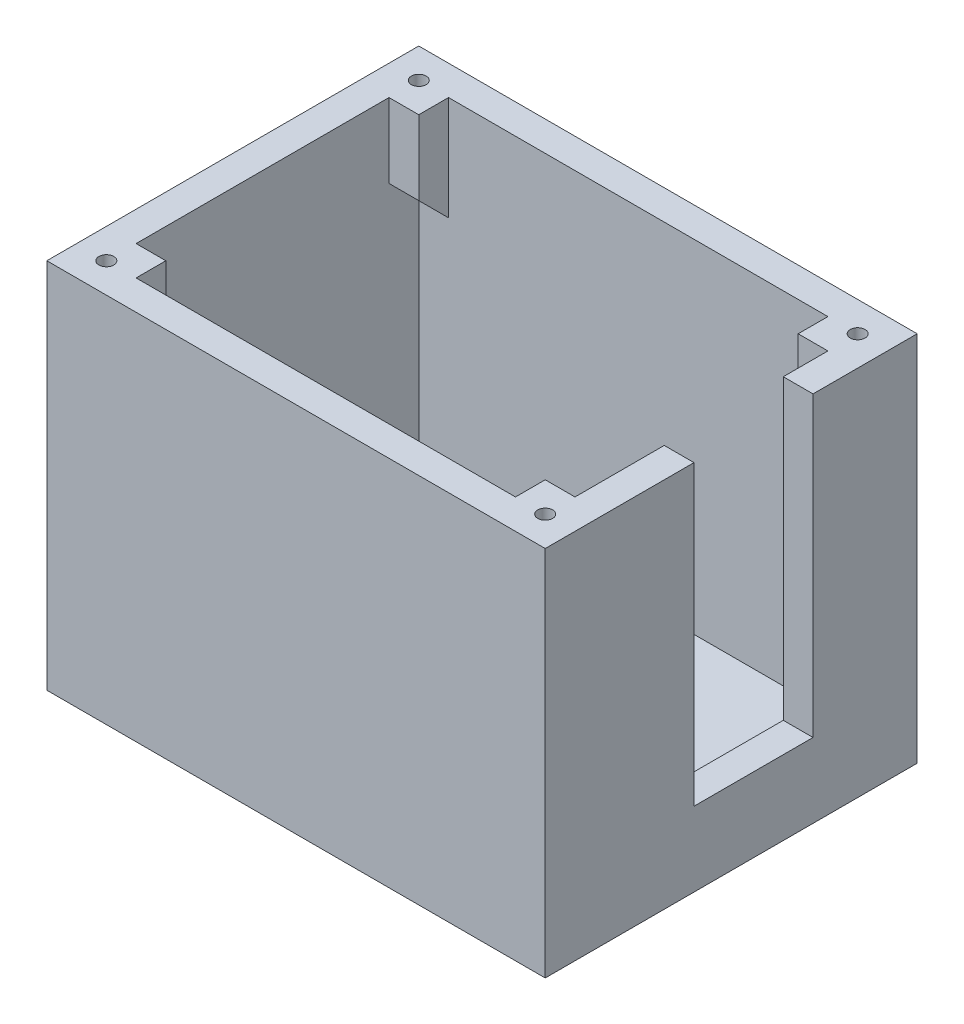
SolidWorks part; units mm, degrees
ref_plane "Front Plane" through (0, 0, 0) normal (0, 0, 1) x (1, 0, 0)
ref_plane "Top Plane" through (0, 0, 0) normal (0, 1, 0) x (1, 0, 0)
ref_plane "Right Plane" through (0, 0, 0) normal (1, 0, 0) x (0, 0, -1)
sketch "Sketch1" plane through (0, 0, 0) normal (0, 1, 0) x (1, 0, 0)
  line L0 (-11.5455, 18.4394) -> (21.9545, 18.4394)
  line L1 (-9.5455, -4.5606) -> (19.9545, -4.5606)
  line L2 (-9.5455, -4.5606) -> (-9.5455, 16.4394)
  line L3 (-9.5455, 16.4394) -> (19.9545, 16.4394)
  line L4 (19.9545, -4.5606) -> (19.9545, 16.4394)
  line L5 (21.9545, -6.5606) -> (21.9545, 18.4394)
  line L6 (-11.5455, -6.5606) -> (21.9545, -6.5606)
  line L7 (-11.5455, -6.5606) -> (-11.5455, 18.4394)
  dimension "D1" = 21
  dimension "D2" = 29.5
  dimension "D3" = 2
extrude "Boss-Extrude1" add sketch "Sketch1" along normal blind 2 contours L1 L4 L3 L2 | L7 L6 L5 L0 L4 L1 L2 L3 region at (5.2045, 0, -18.0214) region at (5.2045, 0, -5.9394)
extrude "Boss-Extrude2" add sketch "Sketch1<3>" along normal offset from surface (25 mm away) 23 up to face at (5.2045, 2, -5.9394) offset beyond the face yes
sketch "Sketch1<3>" plane through (0, 0, 0) normal (0, 1, 0) x (1, 0, 0) same geometry as "Sketch1"
sketch "Sketch2" plane through (0, 25, 0) normal (0, 1, 0) x (1, 0, 0)
  line L0 (19.9545, -4.5606) -> (19.9545, 16.4394) construction
  line L1 (19.9545, 3.4394) -> (21.9545, 3.4394)
  line L2 (19.9545, 3.4394) -> (19.9545, 11.4394)
  line L3 (19.9545, 11.4394) -> (21.9545, 11.4394)
  line L4 (21.9545, 3.4394) -> (21.9545, 11.4394)
  line L5 (21.9545, -6.5606) -> (21.9545, 18.4394) construction
  line L6 (-9.5455, 16.4394) -> (19.9545, 16.4394) construction
  dimension "D1" = 8
  dimension "D2" = 5
extrude "Cut-Extrude1" cut sketch "Sketch2" against normal offset from surface (20 mm away) 3 up to face at (5.2045, 2, -5.9394)
sketch "Sketch3" plane through (0, 25, 0) normal (0, 1, 0) x (1, 0, 0)
  line L1 (-9.5455, 16.4394) -> (-7.5455, 16.4394)
  line L2 (-9.5455, 16.4394) -> (-9.5455, 14.4394)
  line L3 (-9.5455, 14.4394) -> (-7.5455, 14.4394)
  line L4 (-7.5455, 16.4394) -> (-7.5455, 14.4394)
  line L5 (-9.5455, -4.5606) -> (-7.5455, -4.5606)
  line L6 (-9.5455, -4.5606) -> (-9.5455, -2.5606)
  line L7 (-9.5455, -2.5606) -> (-7.5455, -2.5606)
  line L8 (-7.5455, -4.5606) -> (-7.5455, -2.5606)
  line L9 (19.9545, -4.5606) -> (17.9545, -4.5606)
  line L10 (19.9545, -4.5606) -> (19.9545, -2.5606)
  line L11 (19.9545, -2.5606) -> (17.9545, -2.5606)
  line L12 (17.9545, -4.5606) -> (17.9545, -2.5606)
  line L13 (19.9545, 16.4394) -> (17.9545, 16.4394)
  line L14 (19.9545, 16.4394) -> (19.9545, 14.4394)
  line L15 (19.9545, 14.4394) -> (17.9545, 14.4394)
  line L16 (17.9545, 16.4394) -> (17.9545, 14.4394)
  dimension "D1" = 2
  dimension "D2" = 2
  dimension "D3" = 2
  dimension "D4" = 2
  dimension "D5" = 2
  dimension "D6" = 2
  dimension "D7" = 2
  dimension "D8" = 2
extrude "Boss-Extrude3" add sketch "Sketch3" against normal blind 5
chamfer "Chamfer1" distance 2 angle 45 4 edges at (18.9545, 20, 4.5606) (-8.5455, 20, 4.5606) (18.9545, 20, -16.4394) (-8.5455, 20, -16.4394)
sketch "Sketch4" plane through (0, 25, 0) normal (0, 1, 0) x (1, 0, 0)
  line L4 (19.9545, 16.4394) -> (-9.5455, 16.4394)
  line L5 (-9.5455, 16.4394) -> (-9.5455, -4.5606)
  line L6 (-9.5455, -4.5606) -> (19.9545, -4.5606)
  line L7 (19.9545, -4.5606) -> (19.9545, 16.4394)
  line L8 (19.9545, 16.4394) -> (-9.5455, 16.4394)
  line L9 (-9.5455, 16.4394) -> (-9.5455, -4.5606)
  line L10 (-9.5455, -4.5606) -> (19.9545, -4.5606)
  line L11 (19.9545, -4.5606) -> (19.9545, 16.4394)
  circle A0 centre (-9.5455, -4.5606) radius 0.5
  circle A1 centre (-9.5455, 16.4394) radius 0.5
  circle A2 centre (19.9545, -4.5606) radius 0.5
  circle A3 centre (19.9545, 16.4394) radius 0.5
  dimension "D2" = 1
  dimension "D3" = 1
  dimension "D4" = 1
  dimension "D5" = 1
  dimension "D1" = 0
extrude "Cut-Extrude2" cut sketch "Sketch4" against normal blind 5 contours L10 A2 L11 | L11 A2 L10 | L11 A3 L8 | L8 A3 L11 | L8 A1 L9 | L9 A1 L8 | L9 A0 L10 | L10 A0 L9 region at (-9.3332, 25, -16.2272) region at (-9.6162, 25, -16.5101) region at (20.0253, 25, -16.5101) region at (19.7423, 25, -16.2272) region at (-9.3332, 25, 4.3484) region at (-9.6162, 25, 4.6313) region at (20.0253, 25, 4.6313) region at (19.7423, 25, 4.3484)
